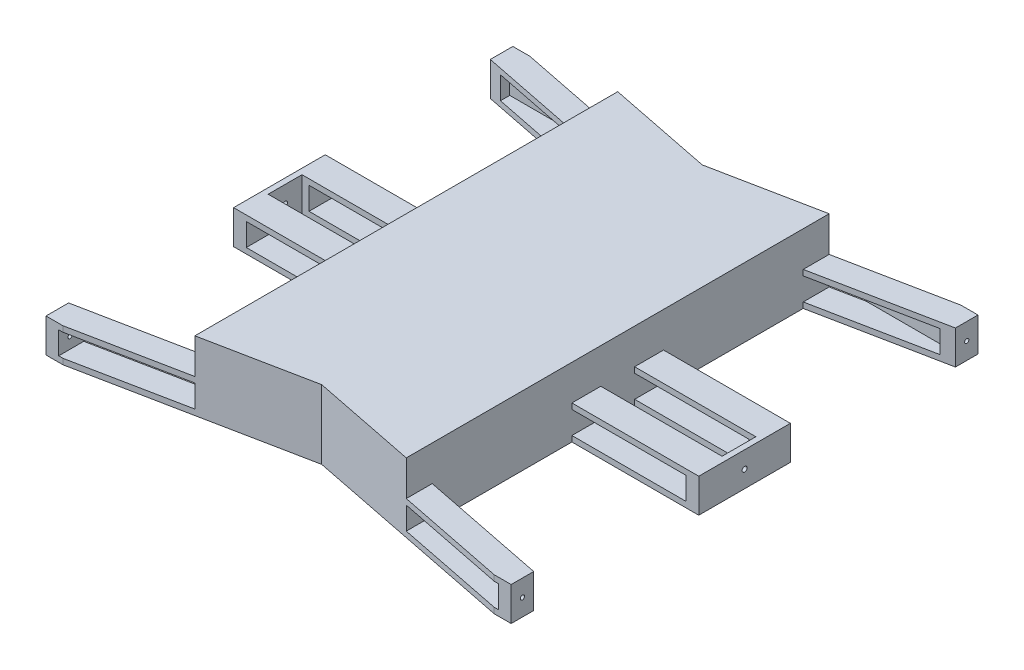
SolidWorks part; units mm, degrees
ref_plane "Front Plane" through (0, 0, 0) normal (0, 0, 1) x (1, 0, 0)
ref_plane "Top Plane" through (0, 0, 0) normal (0, 1, 0) x (1, 0, 0)
ref_plane "Right Plane" through (0, 0, 0) normal (1, 0, 0) x (0, 0, -1)
sketch "Sketch1" plane through (0, 0, 0) normal (0, 1, 0) x (1, 0, 0)
  line L1 (-55, 0) -> (55, 0) construction
  line L2 (165, 32.5) -> (165, -32.5)
  line L3 (165, -32.5) -> (75, -32.5)
  line L4 (75, -32.5) -> (75, -131.6)
  line L5 (75, -131.6) -> (165, -149.6)
  line L6 (165, -149.6) -> (165, -165.6)
  line L7 (165, -165.6) -> (153, -165.6)
  line L8 (153, -165.6) -> (0, -135)
  line L9 (0, -55) -> (0, 55) construction
  line L11 (-165, 32.5) -> (-165, -32.5)
  line L12 (-165, -32.5) -> (-75, -32.5)
  line L13 (-75, -32.5) -> (-75, -131.6)
  line L14 (-75, -131.6) -> (-165, -149.6)
  line L15 (-165, -149.6) -> (-165, -165.6)
  line L16 (-165, -165.6) -> (-153, -165.6)
  line L17 (-153, -165.6) -> (0, -135)
  line L18 (165, 32.5) -> (75, 32.5)
  line L19 (75, 32.5) -> (75, 131.6)
  line L20 (165, 165.6) -> (153, 165.6)
  line L21 (165, 149.6) -> (165, 165.6)
  line L22 (75, 131.6) -> (165, 149.6)
  line L23 (153, 165.6) -> (0, 135)
  line L24 (-165, 149.6) -> (-165, 165.6)
  line L25 (-165, 165.6) -> (-153, 165.6)
  line L26 (-153, 165.6) -> (0, 135)
  line L27 (-75, 131.6) -> (-165, 149.6)
  line L28 (-165, 32.5) -> (-75, 32.5)
  line L29 (-75, 32.5) -> (-75, 131.6)
  line L30 (75, -131.6) -> (75, -150) construction
  line L32 (-75, -131.6) -> (-75, -150) construction
  line L34 (-75, 131.6) -> (-75, 150) construction
  line L36 (75, 131.6) -> (75, 150) construction
  point P21 (165, 0)
  point P33 (-165, 0)
  dimension "D1" = 300
  dimension "D2" = 270
  dimension "D3" = 150
  dimension "D4" = 16
  dimension "D5" = 12
  dimension "D6" = 65
  dimension "D7" = 90
extrude "Boss-Extrude1" add sketch "Sketch1" along normal blind 12 and the other way blind 12
sketch "Sketch2" plane through (0, 0, 165.6) normal (0, 0, 1) x (1, 0, 0)
  line L1 (-156, -8) -> (156, -8)
  line L2 (-156, -8) -> (-156, 8)
  line L3 (-156, 8) -> (156, 8)
  line L4 (156, -8) -> (156, 8)
  line L7 (55, 0) -> (-55, 0) construction
  dimension "D1" = 8
  dimension "D2" = 8
  dimension "D3" = 156
  dimension "D4" = 156
extrude "Cut-Extrude1" cut sketch "Sketch2" against normal blind 320
sketch "Sketch4" plane through (0, 12, 0) normal (0, 1, 0) x (1, 0, 0)
  line L0 (-55, 0) -> (55, 0) construction
  line L1 (-161, 12) -> (-75, 12)
  line L2 (-161, 12) -> (-161, -12)
  line L3 (-161, -12) -> (-75, -12)
  line L4 (-75, 12) -> (-75, -12)
  line L5 (-165, 32.5) -> (-165, -32.5) construction
  line L6 (-75, -32.5) -> (-75, -131.6) construction
  line L7 (0, -55) -> (0, 55) construction
  line L8 (161, -12) -> (75, -12)
  line L9 (75, 12) -> (75, -12)
  line L10 (161, 12) -> (75, 12)
  line L11 (161, 12) -> (161, -12)
  dimension "D1" = 12
  dimension "D2" = 12
  dimension "D3" = 4
extrude "Cut-Extrude2" cut sketch "Sketch4" against normal blind 24
sketch "Sketch6" plane through (0, 0, 0) normal (1, 0, 0) x (0, 0, -1)
  line L0 (-149.6, 0) -> (-165.6, 0) construction
  line L1 (149.6, 0) -> (165.6, 0) construction
  circle A0 centre (-157.6, 0) radius 1.5
  circle A1 centre (157.6, 0) radius 1.5
  point P6 (-157.6, 0)
  point P10 (157.6, 0)
  dimension "D1" = 3
extrude "Cut-Extrude3" cut sketch "Sketch6" against normal through all both and the other way through all
sketch "Sketch7" plane through (165, 0, 0) normal (1, 0, 0) x (0, 0, -1)
  circle A0 centre (0, 0) radius 1.75
  dimension "D1" = 3.5
extrude "Cut-Extrude4" cut sketch "Sketch7" against normal up to surface (330 mm away) up to face at (-165, 0, 0)
sketch "Sketch8" plane through (0, 12, 0) normal (0, 1, 0) x (1, 0, 0)
  line L0 (0, 135) -> (0, -135) construction
  line L1 (156, -12) -> (156, 12) construction
  line L2 (156, 8) -> (144, 8)
  line L3 (156, 8) -> (156, -8)
  line L4 (156, -8) -> (144, -8)
  line L5 (144, 8) -> (144, -8)
  line L6 (-156, 0) -> (165, 0) construction
  line L7 (-156, 12) -> (-156, -12) construction
  line L8 (165, -32.5) -> (165, 32.5) construction
  line L9 (-156, -8) -> (-144, -8)
  line L10 (-144, 8) -> (-144, -8)
  line L11 (-156, 8) -> (-144, 8)
  line L12 (-156, 8) -> (-156, -8)
  point P16 (144, 0)
  dimension "D1" = 16
  dimension "D2" = 12
extrude "Cut-Extrude5" [suppressed] cut sketch "Sketch8" against normal up to surface (5 mm away) up to face at (0, 8, 1.3176)
sketch "Sketch11" plane through (0, 12, 0) normal (0, 1, 0) x (1, 0, 0)
  line L0 (-75, -150) -> (-75, 150)
  line L1 (-153, -165.6) -> (0, -135) construction
  line L2 (0, 135) -> (-153, 165.6) construction
  line L3 (75, 150) -> (75, -150)
  line L4 (153, 165.6) -> (0, 135) construction
  line L5 (0, -135) -> (153, -165.6) construction
  line L6 (75, 32.5) -> (75, 131.6) construction
  line L7 (-75, 131.6) -> (-75, 32.5) construction
  line L8 (0, -135) -> (75, -150)
  line L9 (-75, -150) -> (0, -135)
  line L10 (0, 135) -> (-75, 150)
  line L11 (75, 150) -> (0, 135)
extrude "Cut-Extrude7" cut sketch "Sketch11" against normal up to surface (4 mm away) up to face at (0, 8, 1.3176)
sketch "Sketch12" plane through (0, -8, 0) normal (0, 1, 0) x (1, 0, 0)
  line L0 (-75, 150) -> (-75, -150)
  line L1 (-153, -165.6) -> (0, -135) construction
  line L2 (75, 150) -> (75, -150)
  line L3 (-75, -150) -> (0, -135)
  line L4 (0, -135) -> (75, -150)
  line L5 (-75, 150) -> (0, 135)
  line L6 (0, 135) -> (75, 150)
  line L7 (0, 132.9604) -> (73, 147.5604)
  line L8 (73, 147.5604) -> (73, -147.5604)
  line L9 (0, -132.9604) -> (73, -147.5604)
  line L10 (-73, -147.5604) -> (0, -132.9604)
  line L11 (-73, 147.5604) -> (-73, -147.5604)
  line L12 (-73, 147.5604) -> (0, 132.9604)
  dimension "D1" = 2
extrude "Boss-Extrude2" add sketch "Sketch12" along normal blind 45
sketch "Sketch13" plane through (0, 37, 0) normal (0, 1, 0) x (1, 0, 0)
  line L0 (75, 150) -> (0, 135) construction
  line L1 (0, 135) -> (-75, 150) construction
  line L2 (-75, 150) -> (-75, -150) construction
  line L3 (75, -150) -> (75, 150) construction
  line L4 (0, -135) -> (75, -150) construction
  line L5 (-75, -150) -> (0, -135) construction
  line L6 (75, 150) -> (0, 135)
  line L7 (0, 135) -> (-75, 150)
  line L8 (-75, 150) -> (-75, -150)
  line L9 (75, -150) -> (75, 150)
  line L10 (0, -135) -> (75, -150)
  line L11 (-75, -150) -> (0, -135)
extrude "Boss-Extrude3" add sketch "Sketch13" against normal blind 5
equation "\"A\"= 4"
equation "\"D1@Boss-Extrude1\"=3*\"A\""
equation "\"D2@Boss-Extrude1\"=3*\"A\""
equation "\"D1@Sketch2\"=2*\"A\""
equation "\"D2@Sketch2\"=2*\"A\""
equation "\"D1@Sketch4\"=3*\"A\""
equation "\"D2@Sketch4\"=3*\"A\""
equation "\"D3@Sketch4\"=\"A\""
equation "\"D1@Cut-Extrude2\"=6*\"A\""
equation "\"D1@Cut-Extrude1\"=80*\"A\""
equation "\"D3@Sketch2\"=\"A\" * 39"
equation "\"D4@Sketch2\"=\"A\" * 39"
